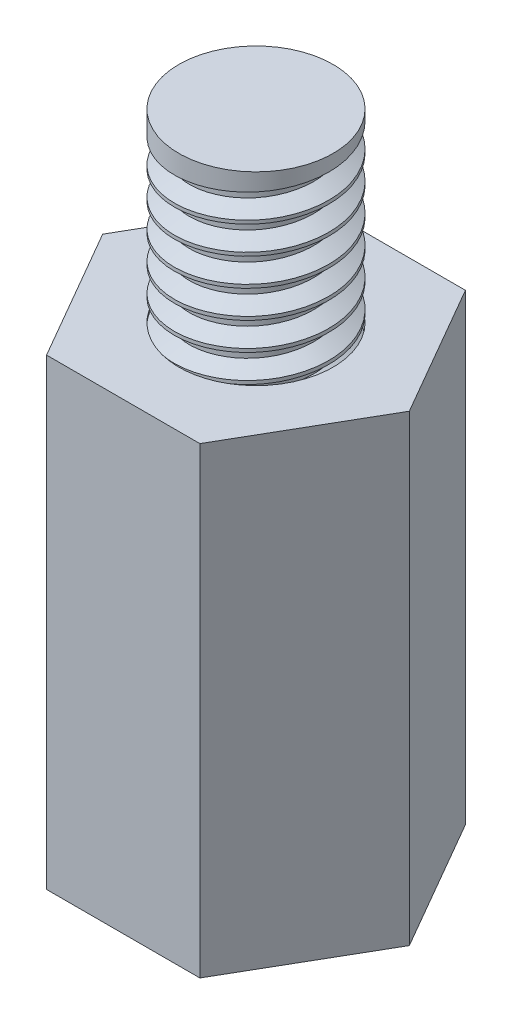
SolidWorks part; units mm, degrees
material "1060 Alloy"
ref_plane "Front Plane" through (0, 0, 0) normal (0, 0, 1) x (1, 0, 0)
ref_plane "Top Plane" through (0, 0, 0) normal (0, 1, 0) x (1, 0, 0)
ref_plane "Right Plane" through (0, 0, 0) normal (1, 0, 0) x (0, 0, -1)
sketch "Sketch1" plane through (0, 0, 0) normal (0, 1, 0) x (1, 0, 0)
  line L1 (2.4846, 0) -> (1.2423, 2.1517)
  line L2 (1.2423, 2.1517) -> (-1.2423, 2.1517)
  line L3 (-1.2423, 2.1517) -> (-2.4846, 0)
  line L4 (-2.4846, 0) -> (-1.2423, -2.1517)
  line L5 (-1.2423, -2.1517) -> (1.2423, -2.1517)
  line L6 (1.2423, -2.1517) -> (2.4846, 0)
  circle A0 centre (0, 0) radius 1.25
  circle A1 centre (0, 0) radius 2.1517 construction
extrude "Boss-Extrude1" add sketch "Sketch1" along normal blind 7.5 contours L5 L6 L1 L2 L3 L4 A0 | A0 region at (1.8065, 0, 1.043) region at (0, 0, 0)
extrude "Cut-Extrude1" cut sketch "Sketch1<3>" along normal blind 5 contours A0 region at (0, 0, 0)
sketch "Sketch1<3>" plane through (0, 0, 0) normal (0, 1, 0) x (1, 0, 0) same geometry as "Sketch1"
sketch "Sketch2" plane through (0, 7.5, 0) normal (0, 1, 0) x (1, 0, 0)
  circle A0 centre (0, 0) radius 1.25
extrude "Boss-Extrude2" add sketch "Sketch2" along normal blind 3 and the other way blind 1
thread "Thread1" pitch 0.45 method cut profile "Thread Profile1" start angle 0, offset 0, length 0, pitch 0.45, diameter 2.5
ref_plane "Plane1" through (-1.25, 10.5, 0) normal (0, 0, 1) x (-1, 0, 0)
sketch "Thread Profile1" plane through (-1.25, 10.5, 0) normal (0, 0, 1) x (-1, 0, 0)
  line L0 (0, 0) -> (0, 0.45) construction
  line L11 (0, 0) -> (0, 0.3937)
  line L12 (0, 0.3937) -> (-0.2436, 0.2531)
  line L13 (-0.2436, 0.2531) -> (-0.2436, 0.1406)
  line L15 (-0.2436, 0.1406) -> (0, 0)
  line L17 (-0.2436, 0.1969) -> (0, 0.1969) construction
  point P2 (0, 0)
  dimension "Pitch" = 0.45
  dimension "Profile_Angle" = 60
  dimension "Profile_Land" = 0.1125
  dimension "Profile_Height" = 0.2436
thread "Thread2" pitch 0.45 method extrude profile "Thread Profile2" start angle 0, offset 0, length 2, pitch 0.45, diameter 2.5
ref_plane "Plane2" through (1.25, 0, 0) normal (0, 0, 1) x (1, 0, 0)
sketch "Thread Profile2" plane through (1.25, 0, 0) normal (0, 0, 1) x (1, 0, 0)
  line L0 (0, 0) -> (0, 0.45) construction
  line L11 (0, 0) -> (0, 0.3937)
  line L12 (0, 0.3937) -> (-0.2436, 0.2531)
  line L13 (-0.2436, 0.2531) -> (-0.2436, 0.1406)
  line L15 (-0.2436, 0.1406) -> (0, 0)
  line L17 (-0.2436, 0.1969) -> (0, 0.1969) construction
  point P2 (0, 0)
  dimension "Pitch" = 0.45
  dimension "Profile_Angle" = 60
  dimension "Profile_Land" = 0.1125
  dimension "Profile_Height" = 0.2436
